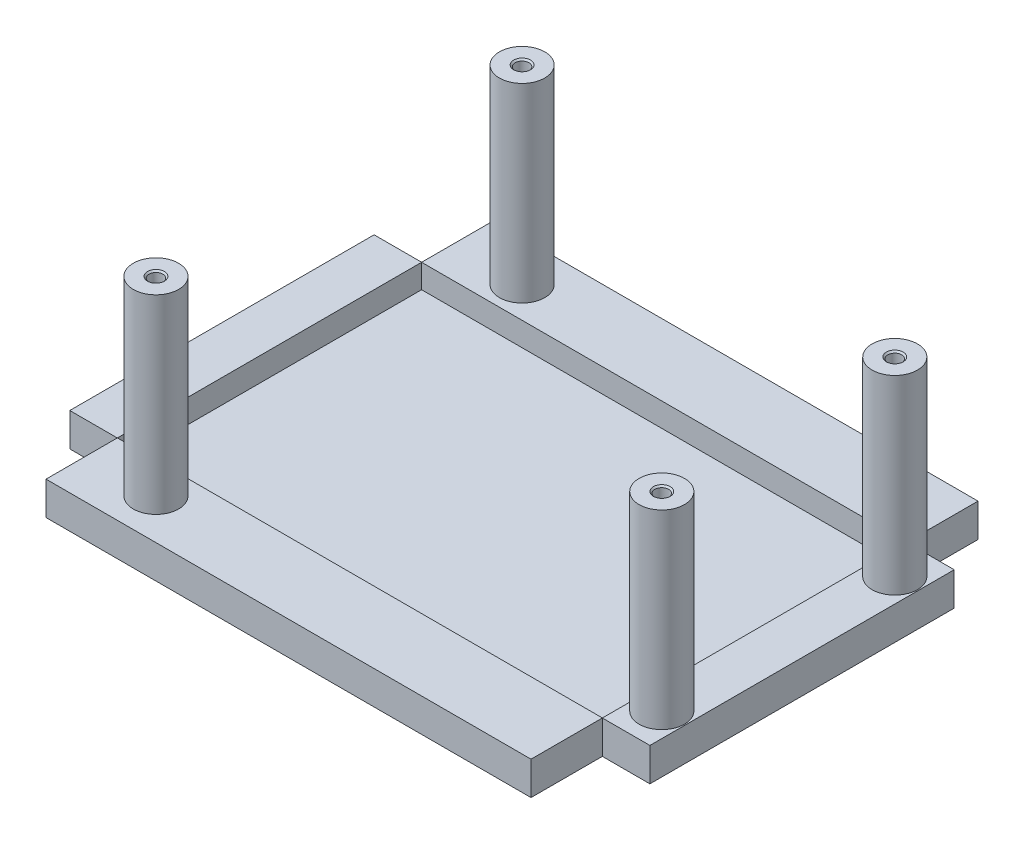
SolidWorks part; units mm, degrees
ref_plane "前视基准面" through (0, 0, 0) normal (0, 0, 1) x (1, 0, 0)
ref_plane "上视基准面" through (0, 0, 0) normal (0, 1, 0) x (1, 0, 0)
ref_plane "右视基准面" through (0, 0, 0) normal (1, 0, 0) x (0, 0, -1)
other "Configuration Table"
sketch "草图1" plane through (0, 0, 0) normal (0, 1, 0) x (1, 0, 0)
  line L0 (0, 64) -> (0, 79)
  line L1 (0, 0) -> (102, 0)
  line L2 (0, 0) -> (0, 64)
  line L3 (0, 64) -> (102, 64)
  line L4 (102, 0) -> (102, 64)
  line L5 (0, 0) -> (0, -15)
  line L6 (0, 79) -> (102, 79)
  line L7 (102, 79) -> (102, 64)
  line L8 (102, 0) -> (102, -15)
  line L9 (102, -15) -> (0, -15)
  line L11 (0, 64) -> (-10, 64)
  line L12 (0, 64) -> (0, 0)
  line L13 (0, 0) -> (-10, 0)
  line L14 (-10, 64) -> (-10, 0)
  line L15 (102, 64) -> (112, 64)
  line L16 (102, 64) -> (102, 0)
  line L17 (102, 0) -> (112, 0)
  line L18 (112, 64) -> (112, 0)
  point P13 (0, 0)
  point P14 (0, 0)
  dimension "D1" = 64
  dimension "D2" = 102
  dimension "D3" = 15
  dimension "D4" = 15
  dimension "D5" = 10
  dimension "D6" = 10
extrude "凸台-拉伸7" add sketch "草图1" along normal blind 7 contours L11 L14 L13 L2 | L7 L6 L0 L3 | L18 L15 L4 L17 | L9 L8 L1 L5 | L2 L1 L4 L3 region at (51, 0, -71.5) region at (-5, 0, -32) region at (51, 0, 7.5) region at (107, 0, -32)
sketch "草图3" plane through (0, 7, 0) normal (0, 1, 0) x (1, 0, 0)
  line L5 (102, 63.99) -> (102, 0.01)
  line L6 (102, 0.01) -> (0, 0.01)
  line L7 (0, 0.01) -> (0, 63.99)
  line L8 (0, 63.99) -> (102, 63.99)
  dimension "D1" = 63.98
  dimension "D2" = 0.01
extrude "切除-拉伸5" cut sketch "草图3" against normal blind 5
sketch "草图4" plane through (0, 7, 0) normal (0, 1, 0) x (1, 0, 0)
  line L0 (112, 32) -> (102, 32) construction
  line L1 (112, 64) -> (112, 0) construction
  line L2 (102, 0.01) -> (102, 63.99) construction
  line L3 (112, 4.5) -> (112, 59.5) construction
  line L4 (112, 59.5) -> (102, 59.5) construction
  line L5 (112, 4.5) -> (102, 4.5) construction
  line L6 (107, 59.5) -> (107, 56.5) construction
  line L7 (102, 64) -> (112, 64) construction
  circle A0 centre (107, 56.5) radius 4.7719
  circle A1 centre (107, 7.5) radius 4.7719
  dimension "D2" = 9.5438
  dimension "D1" = 7.5
extrude "凸台-拉伸10" add sketch "草图4" along normal blind 40
sketch "草图9" plane through (0, 47, 0) normal (0, 1, 0) x (1, 0, 0)
  circle A0 centre (107, 56.5) radius 1.75
  circle A1 centre (107, 7.5) radius 1.75
  point P0 (107, 56.5)
  point P3 (107, 7.5)
hole_wizard "M3.5 螺纹孔1" positions "草图9" profile "草图10" tap size "M3.5" standard "GB"
cosmetic thread "孔螺蚊线1"
cosmetic thread "孔螺蚊线2"
sketch "草图10" plane through (107, 47, -56.5) normal (1, 0, 0) x (0, 0, 1)
  line L0 (0, 0) -> (0, 10.8712)
  line L1 (0, 10.8712) -> (1.45, 10)
  line L2 (1.45, 10) -> (1.45, 0.325)
  line L3 (1.45, 0.325) -> (1.775, 0)
  line L5 (1.775, 0) -> (0, 0)
  line L6 (-1.45, 0.325) -> (-1.775, 0) construction
  line L10 (0, 10.8712) -> (-1.45, 10) construction
  line L11 (0, -6.35) -> (0, 107.95) construction
  dimension "螺纹孔钻头直径" = 2.9
  dimension "螺纹孔钻头深度" = 10
  dimension "近端锥形沉头孔直径" = 3.55
  dimension "近端锥形沉头孔角度" = 90
  dimension "导头角度" = 118
sketch "草图11" plane through (0, 7, 0) normal (0, 1, 0) x (1, 0, 0)
  line L1 (0, 64) -> (0, 79) construction
  line L3 (0, 79) -> (0, 70.5) construction
  line L4 (0, 70.5) -> (79.226, 70.5) construction
  line L5 (-10, 32) -> (112, 32) construction
  line L6 (-10, 64) -> (-10, 0) construction
  line L7 (112, 64) -> (112, 0) construction
  line L8 (0, 79) -> (102, 79) construction
  circle A0 centre (14.6238, 70.5) radius 4.77
  circle A2 centre (14.6238, -6.5) radius 4.77
  dimension "D1" = 8.5
  dimension "D2" = 9.54
  dimension "D3" = 14.6238
extrude "凸台-拉伸11" add sketch "草图11" along normal blind 40 contours A0
extrude "凸台-拉伸12" add sketch "草图11<3>" along normal blind 40
sketch "草图11<3>" plane through (0, 7, 0) normal (0, 1, 0) x (1, 0, 0) same geometry as "草图11"
sketch "草图13" plane through (0, 47, 0) normal (0, 1, 0) x (1, 0, 0)
  circle A0 centre (14.6238, 70.5) radius 1.75
  circle A1 centre (14.6238, -6.5) radius 1.75
  point P0 (14.6238, 70.5)
  point P3 (14.6238, -6.5)
hole_wizard "M3.5 螺纹孔2" positions "草图13" profile "草图14" tap size "M3.5" standard "GB"
cosmetic thread "孔螺蚊线3"
cosmetic thread "孔螺蚊线4"
sketch "草图14" plane through (14.6238, 47, -70.5) normal (1, 0, 0) x (0, 0, 1)
  line L0 (0, 0) -> (0, 10.8712)
  line L1 (0, 10.8712) -> (1.45, 10)
  line L2 (1.45, 10) -> (1.45, 0.325)
  line L3 (1.45, 0.325) -> (1.775, 0)
  line L5 (1.775, 0) -> (0, 0)
  line L6 (-1.45, 0.325) -> (-1.775, 0) construction
  line L10 (0, 10.8712) -> (-1.45, 10) construction
  line L11 (0, -6.35) -> (0, 107.95) construction
  dimension "螺纹孔钻头直径" = 2.9
  dimension "螺纹孔钻头深度" = 10
  dimension "近端锥形沉头孔直径" = 3.55
  dimension "近端锥形沉头孔角度" = 90
  dimension "导头角度" = 118
